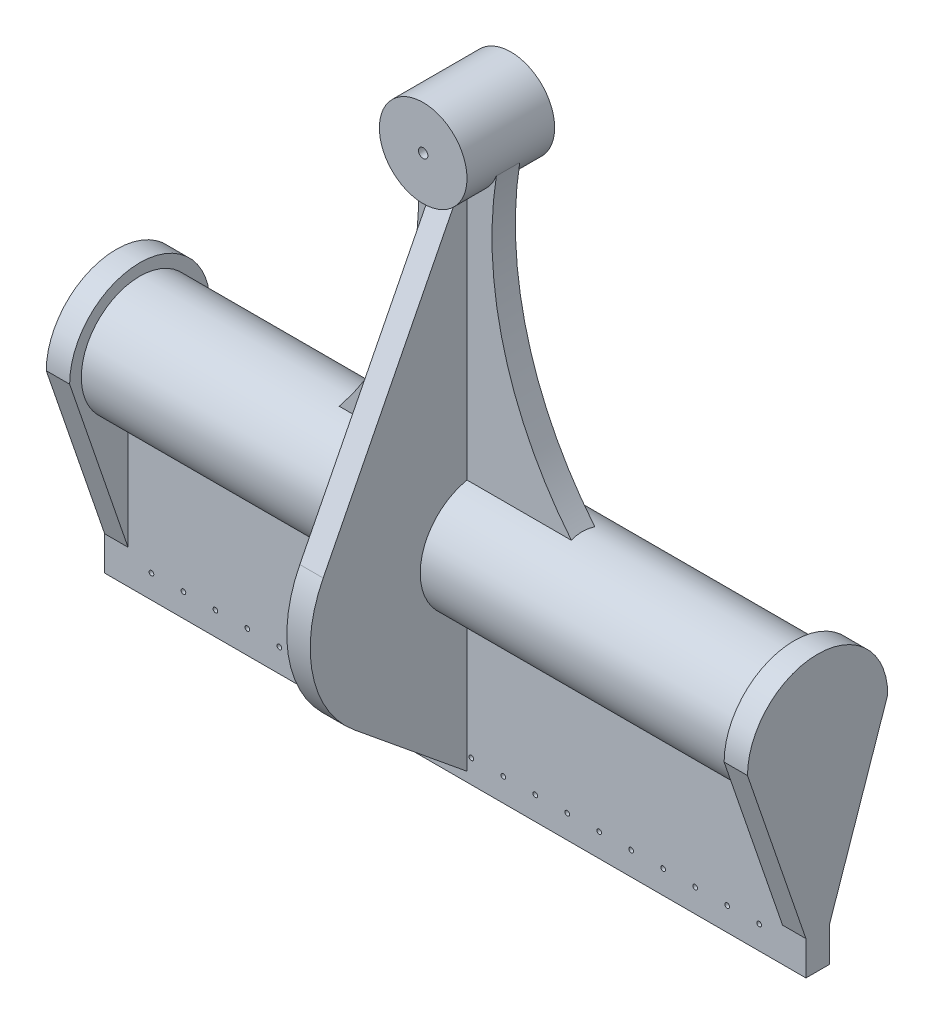
SolidWorks part; units mm, degrees
ref_plane "Front Plane" through (0, 0, 0) normal (1, 0, 0) x (0, 1, 0)
ref_plane "Top Plane" through (0, 0, 0) normal (0, 0, 1) x (0, 1, 0)
ref_plane "Right Plane" through (0, 0, 0) normal (0, 1, 0) x (-1, 0, 0)
sketch "Sketch1" plane through (0, 0, 0) normal (0, 0, 1) x (0, 1, 0)
  line L1 (-44.45, -76.2) -> (0, -76.2)
  line L2 (-44.45, -76.2) -> (-44.45, 76.2)
  line L3 (-44.45, 76.2) -> (0, 76.2)
  line L4 (0, -76.2) -> (0, 76.2)
  line L5 (-44.45, -76.2) -> (0, 76.2) construction
  line L6 (-44.45, 76.2) -> (0, -76.2) construction
  circle A0 centre (-39.37, -66.04) radius 0.508
  circle A1 centre (-39.37, -59.0884) radius 0.508
  circle A2 centre (-39.37, -52.1368) radius 0.508
  circle A3 centre (-39.37, -45.1853) radius 0.508
  circle A4 centre (-39.37, -38.2337) radius 0.508
  circle A5 centre (-39.37, -31.2821) radius 0.508
  circle A6 centre (-39.37, -24.3305) radius 0.508
  circle A7 centre (-39.37, -17.3789) radius 0.508
  circle A8 centre (-39.37, -10.4274) radius 0.508
  circle A9 centre (-39.37, -3.4758) radius 0.508
  circle A10 centre (-39.37, 3.4758) radius 0.508
  circle A11 centre (-39.37, 10.4274) radius 0.508
  circle A12 centre (-39.37, 17.3789) radius 0.508
  circle A13 centre (-39.37, 24.3305) radius 0.508
  circle A14 centre (-39.37, 31.2821) radius 0.508
  circle A15 centre (-39.37, 38.2337) radius 0.508
  circle A16 centre (-39.37, 45.1853) radius 0.508
  circle A17 centre (-39.37, 52.1368) radius 0.508
  circle A18 centre (-39.37, 59.0884) radius 0.508
  circle A19 centre (-39.37, 66.04) radius 0.508
  point P0 (-22.225, 0)
extrude "Boss-Extrude1" add sketch "Sketch1" along normal blind 2.54 and the other way blind 2.54
sketch "Sketch2" plane through (0, 0, 0) normal (1, 0, 0) x (0, 1, 0)
  circle A0 centre (0, 0) radius 12.7
extrude "Boss-Extrude2" add sketch "Sketch2" along normal blind 76.2 and the other way blind 76.2
sketch "Sketch3" plane through (0, 0, 0) normal (1, 0, 0) x (0, 1, 0)
  line L0 (0, 15.24) -> (-44.45, 0)
  line L1 (-44.45, 0) -> (0, -15.24)
  arc A0 (0, -15.24) -> (0, 15.24) centre (0, 0) ccw
extrude "Boss-Extrude3" add sketch "Sketch3" along normal blind 5.08 from offset 71.12
sketch "Sketch4" plane through (0, 0, 0) normal (1, 0, 0) x (0, 1, 0)
  line L0 (0, 15.24) -> (-44.45, 0)
  line L1 (-44.45, 0) -> (0, -15.24)
  arc A0 (0, -15.24) -> (0, 15.24) centre (0, 0) ccw
extrude "Boss-Extrude4" add sketch "Sketch4" against normal blind 5.08 from offset 71.12 offset against normal yes
sketch "Sketch5" plane through (0, 0, 0) normal (0, 0, 1) x (0, 1, 0)
  line L0 (0, -38.1) -> (0, 38.1)
  line L1 (76.2, 9.525) -> (76.2, -9.525)
  arc A0 (0, 38.1) -> (76.2, 9.525) centre (60.8501, 84.4794) ccw
  arc A1 (76.2, -9.525) -> (0, -38.1) centre (60.8501, -84.4794) ccw
extrude "Boss-Extrude5" add sketch "Sketch5" along normal blind 2.54 and the other way blind 2.54
sketch "Sketch6" plane through (0, 0, 0) normal (0, 0, 1) x (0, 1, 0)
  circle A0 centre (76.2, 0) radius 9.525
  circle A1 centre (76.2, 0) radius 1.016
extrude "Boss-Extrude6" add sketch "Sketch6" along normal blind 9.525 and the other way blind 9.525
sketch "Sketch7" plane through (0, 0, 0) normal (1, 0, 0) x (0, 1, 0)
  line L0 (-44.45, 0) -> (-22.3144, 27.0642)
  line L1 (-44.45, -2.54) -> (-44.45, 2.54) construction
  line L2 (9.6272, 33.7968) -> (76.2, 0)
  line L3 (76.2, 0) -> (3.0481, -14.9321)
  line L4 (-12.1784, -13.4534) -> (-44.45, 0)
  arc A0 (-22.3144, 27.0642) -> (9.6272, 33.7968) centre (-2.1595, 10.5796) cw
  arc A1 (0, -15.24) -> (0, 15.24) centre (0, 0) ccw construction
  arc A2 (3.0481, -14.9321) -> (-12.1784, -13.4534) centre (-2.1595, 10.5796) cw
extrude "Boss-Extrude7" add sketch "Sketch7" along normal blind 2.54 and the other way blind 2.54
